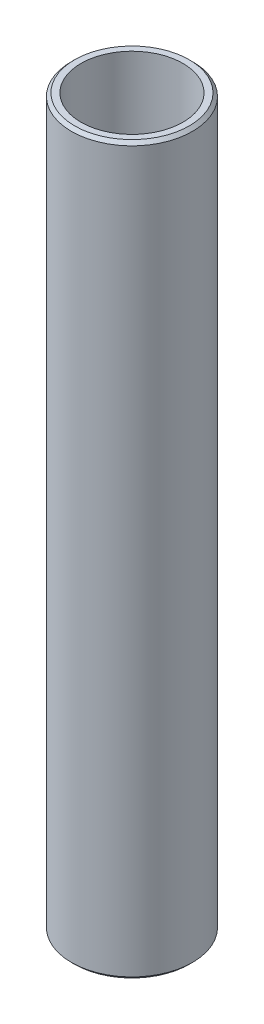
SolidWorks part; units mm, degrees
ref_plane "Front Plane" through (0, 0, 0) normal (0, 0, 1) x (1, 0, 0)
ref_plane "Top Plane" through (0, 0, 0) normal (0, 1, 0) x (1, 0, 0)
ref_plane "Right Plane" through (0, 0, 0) normal (1, 0, 0) x (0, 0, -1)
sketch "Sketch1" plane through (0, 0, 0) normal (0, 1, 0) x (1, 0, 0)
  circle A0 centre (0, 0) radius 50
  dimension "SHAFT_OD" = 100
extrude "Boss-Extrude1" add sketch "Sketch1" along normal blind 600
sketch "Sketch2" plane through (0, 0, 0) normal (0, 1, 0) x (1, 0, 0)
  circle A0 centre (0, 0) radius 42.1363
  dimension "BORE_D" = 84.2725
extrude "Cut-Extrude1" cut sketch "Sketch2" along normal through all
chamfer "Chamfer1" distance 2.6284 angle 45 2 edges at (0, 600, 50) (0, 0, 50)
